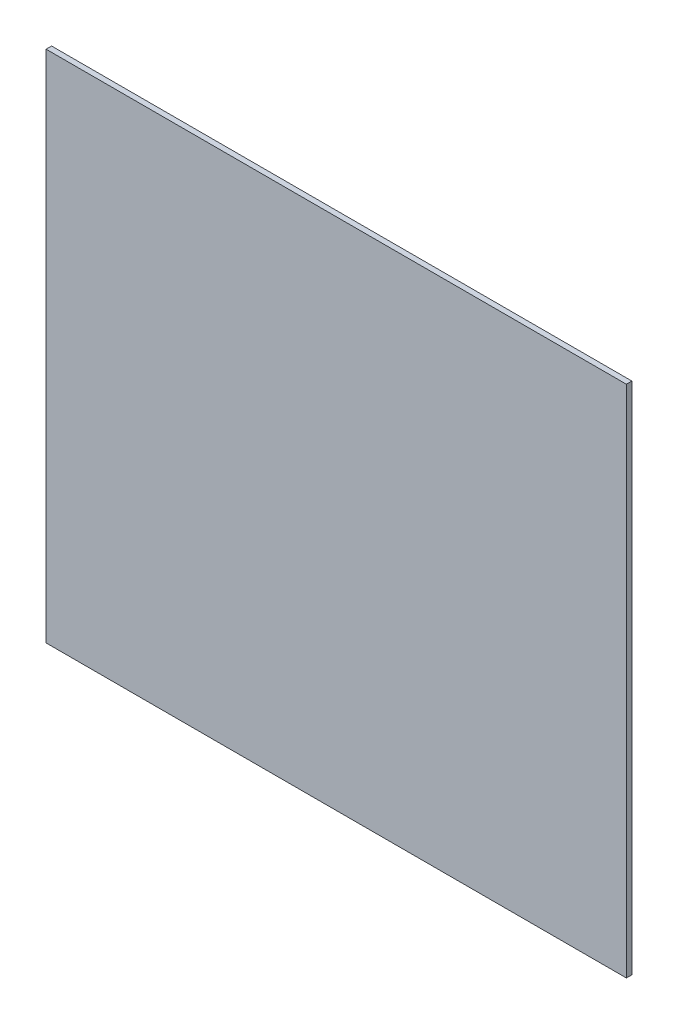
SolidWorks part; units mm, degrees
ref_plane "Front Plane" through (0, 0, 0) normal (0, 0, 1) x (1, 0, 0)
ref_plane "Top Plane" through (0, 0, 0) normal (0, 1, 0) x (1, 0, 0)
ref_plane "Right Plane" through (0, 0, 0) normal (1, 0, 0) x (0, 0, -1)
sketch "Sketch1" plane through (0, 0, 0) normal (0, 0, 1) x (1, 0, 0)
  line L1 (-158, -140) -> (158, -140)
  line L2 (-158, -140) -> (-158, 140)
  line L3 (-158, 140) -> (158, 140)
  line L4 (158, -140) -> (158, 140)
  line L5 (-158, -140) -> (158, 140) construction
  line L6 (-158, 140) -> (158, -140) construction
  point P0 (0, 0)
  dimension "D1" = 316
  dimension "D2" = 280
extrude "Boss-Extrude1" add sketch "Sketch1" along normal blind 3
equation "\"PCLength\"= 316mm'Length across I/O from PS to GPU"
equation "\"PCWidth\"= 242mm'Distance of longest part parallel to GPU(ussually GPU)"
equation "\"PCHeight\"= 178mm'Tallest point with mobo laying flat"
equation "\"WallThickness\"= 9mm'Thickness of each outer tank wall"
equation "\"ThermoBarrierThickness\"= 3mm'Thickness of barrier between hot side and cold side"
equation "\"HotSideGap\"= 25mm'Space in the hot side for a pump"
equation "\"PCClearance\"= 30mm'Clearance from top of tank to top of PC"
equation "\"RadiatorHeight\"= 275mm'Final Height from ground of radiators"
equation "\"D1@Sketch1\"=\"PCLength\""
equation "\"D2@Sketch1\"=\"RadiatorHeight\" + 5"
equation "\"D1@Boss-Extrude1\"=\"ThermoBarrierThickness\""
